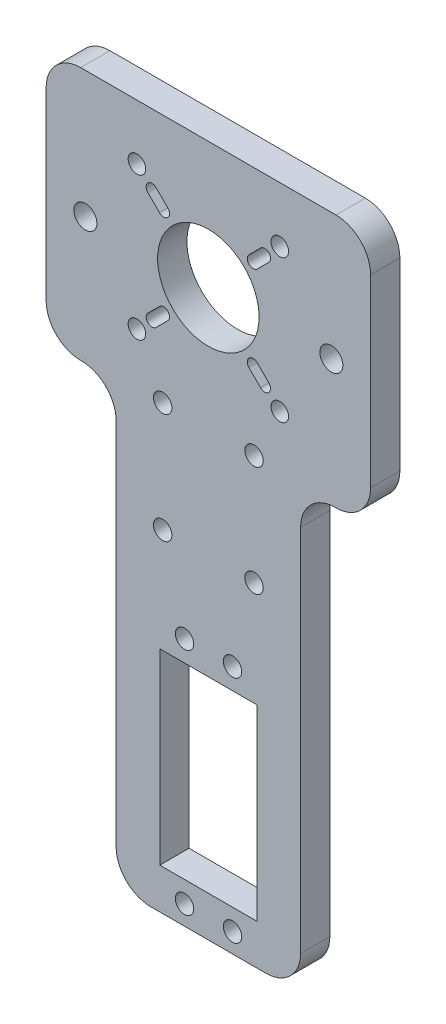
SolidWorks part; units mm, degrees
ref_plane "Front Plane" through (0, 0, 0) normal (0, 0, 1) x (1, 0, 0)
ref_plane "Top Plane" through (0, 0, 0) normal (0, 1, 0) x (1, 0, 0)
ref_plane "Right Plane" through (0, 0, 0) normal (1, 0, 0) x (0, 0, -1)
sketch "Sketch1" plane through (0, 0, 0) normal (0, 0, 1) x (1, 0, 0)
  line L0 (0, 0) -> (0, 11.938) construction
  line L3 (-20, -84) -> (20, -84)
  line L5 (-21.209, 78.74) -> (21.209, -78.74) construction
  line L6 (-21.209, -78.74) -> (21.209, 78.74) construction
  line L7 (0, 11.938) -> (9.906, 11.938) construction
  line L8 (0, 0) -> (0, 38.5) construction
  line L9 (0, 38.5) -> (15.494, 38.5) construction
  line L10 (15.494, 38.5) -> (15.494, 53.994) construction
  line L11 (0, 38.5) -> (10.9602, 49.4602) construction
  line L12 (9.7029, 48.2029) -> (12.2174, 50.7174) construction
  line L13 (8.8049, 49.1009) -> (11.3194, 51.6154)
  line L14 (10.6009, 47.3049) -> (13.1154, 49.8194)
  line L17 (9.7029, 28.7971) -> (12.2174, 26.2826) construction
  line L24 (0, 0) -> (0, -30) construction
  line L25 (0, -30) -> (-5.1689, -30) construction
  line L26 (0, -30) -> (0, -54.892) construction
  line L27 (0, 38.5) -> (-26.67, 38.5) construction
  line L28 (-10.541, -34.572) -> (10.541, -34.572)
  line L29 (-10.541, -34.572) -> (-10.541, -75.212)
  line L30 (-10.541, -75.212) -> (10.541, -75.212)
  line L31 (10.541, -34.572) -> (10.541, -75.212)
  line L32 (-10.541, -34.572) -> (10.541, -75.212) construction
  line L33 (-10.541, -75.212) -> (10.541, -34.572) construction
  line L40 (-20, 11) -> (-20, -84)
  line L41 (-35.179, 11) -> (-20, 11)
  line L42 (-35.179, 11) -> (-35.179, 66)
  line L43 (-35.179, 66) -> (35.179, 66)
  line L44 (35.179, 11) -> (35.179, 66)
  line L45 (-35.179, 11) -> (35.179, 66) construction
  line L46 (-35.179, 66) -> (35.179, 11) construction
  line L47 (20, 11) -> (20, -84)
  line L48 (20, 11) -> (35.179, 11)
  line L67 (10.6009, 29.6951) -> (13.1154, 27.1806)
  line L70 (8.8049, 27.8991) -> (11.3194, 25.3846)
  line L73 (-9.7029, 28.7971) -> (-12.2174, 26.2826) construction
  line L74 (-8.8049, 27.8991) -> (-11.3194, 25.3846)
  line L75 (-10.6009, 29.6951) -> (-13.1154, 27.1806)
  line L76 (-9.7029, 48.2029) -> (-12.2174, 50.7174) construction
  line L77 (-10.6009, 47.3049) -> (-13.1154, 49.8194)
  line L78 (-8.8049, 49.1009) -> (-11.3194, 51.6154)
  circle A0 centre (9.906, 11.938) radius 2
  circle A1 centre (-9.906, 11.938) radius 2
  circle A2 centre (-9.906, -11.938) radius 2
  circle A3 centre (9.906, -11.938) radius 2
  circle A4 centre (0, 38.5) radius 11
  circle A5 centre (15.494, 53.994) radius 1.905
  arc A9 (8.8049, 49.1009) -> (10.6009, 47.3049) centre (9.7029, 48.2029) ccw
  arc A10 (13.1154, 49.8194) -> (11.3194, 51.6154) centre (12.2174, 50.7174) ccw
  circle A17 centre (-5.1689, -30) radius 2
  circle A18 centre (5.2451, -30) radius 2
  circle A19 centre (5.2451, -79.784) radius 2
  circle A20 centre (-5.1689, -79.784) radius 2
  circle A21 centre (-26.67, 38.5) radius 2.5
  circle A28 centre (26.67, 38.5) radius 2.5
  circle A73 centre (15.494, 23.006) radius 1.905
  arc A74 (10.6009, 29.6951) -> (8.8049, 27.8991) centre (9.7029, 28.7971) ccw
  arc A75 (11.3194, 25.3846) -> (13.1154, 27.1806) centre (12.2174, 26.2826) ccw
  circle A76 centre (-15.494, 23.006) radius 1.905
  arc A77 (-8.8049, 27.8991) -> (-10.6009, 29.6951) centre (-9.7029, 28.7971) ccw
  arc A78 (-13.1154, 27.1806) -> (-11.3194, 25.3846) centre (-12.2174, 26.2826) ccw
  circle A79 centre (-15.494, 53.994) radius 1.905
  arc A80 (-10.6009, 47.3049) -> (-8.8049, 49.1009) centre (-9.7029, 48.2029) ccw
  arc A81 (-11.3194, 51.6154) -> (-13.1154, 49.8194) centre (-12.2174, 50.7174) ccw
  point P0 (0, 0)
  point P30 (10.9602, 49.4602)
  point P39 (10.9602, 27.5398)
  point P48 (-10.9602, 27.5398)
  point P57 (-10.9602, 49.4602)
  point P76 (0, 38.5)
  point P83 (-27.5895, 11)
  dimension "D3" = 4
  dimension "D6" = 22
  dimension "D9" = 3.81
  dimension "D15" = 1.27
  dimension "D27" = 4
  dimension "D30" = 5
  dimension "D11" = 55
  dimension "D31" = 9.906
  dimension "D1" = 11.938
  dimension "D2" = 9.906
  dimension "D5" = 38.5
  dimension "D7" = 15.494
  dimension "D8" = 15.494
  dimension "D13" = 95
  dimension "D14" = 45
  dimension "D16" = 1.778
  dimension "D17" = 15.5
  dimension "D19" = 30
  dimension "D20" = 5.1689
  dimension "D23" = 24.892
  dimension "D24" = 40.64
  dimension "D25" = 21.082
  dimension "D28" = 70.358
  dimension "D29" = 26.67
  dimension "D32" = 11.938
  dimension "D12" = 40
  dimension "D26" = 2
  dimension "D4" = 2
  dimension "D21" = 2
  dimension "D22" = 2
  dimension "D10" = 4
extrude "Boss-Extrude1" add sketch "Sketch1" along normal mid plane 6.35 contours A20 L3 A19 L47 L48 L44 L43 L42 L41 L40 A81 L78 A80 L77 A79 A78 L75 A77 L74 A76 A75 L70 A74 L67 A73 L28 L31 L30 L29 A0 A1 A2 A3 A4 A5 region at (-0.0003, 6.4607, 0)
fillet "Fillet1" radius 7.5 8 edges at (-20, -84, 0) (20, -84, 0) (20, 11, 0) (35.179, 11, 0) (35.179, 66, 0) (-20, 11, 0) (-35.179, 11, 0) (-35.179, 66, 0)
